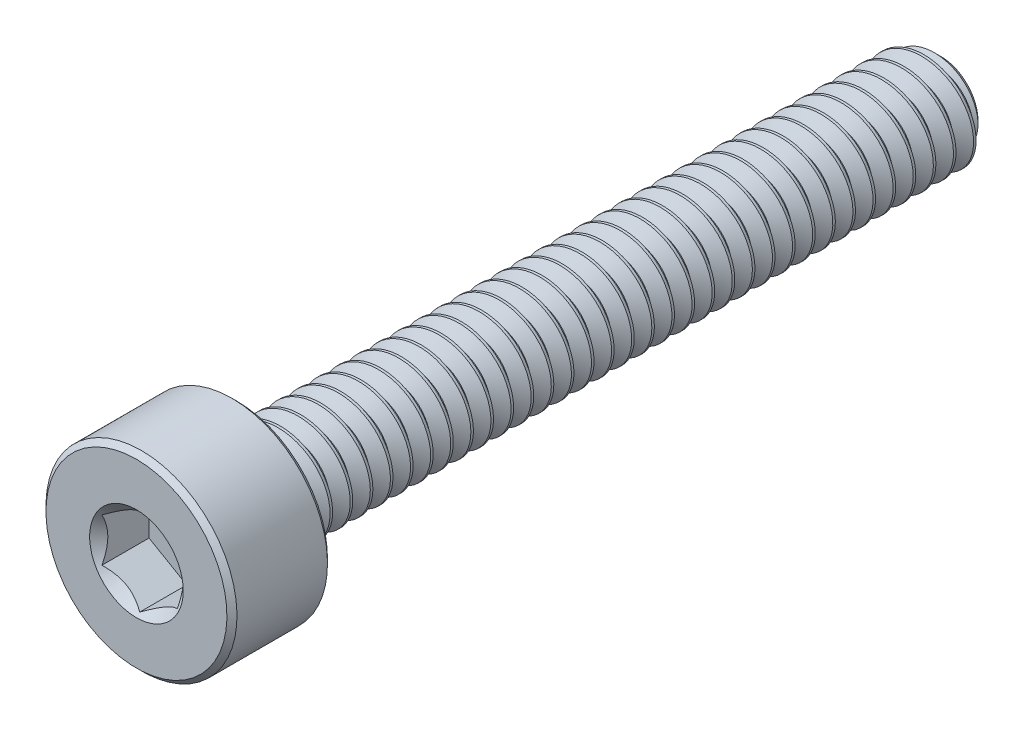
SolidWorks part; units mm, degrees
ref_plane "Front Plane" through (0, 0, 0) normal (0, 0, 1) x (1, 0, 0)
ref_plane "Top Plane" through (0, 0, 0) normal (0, 1, 0) x (1, 0, 0)
ref_plane "Right Plane" through (0, 0, 0) normal (1, 0, 0) x (0, 0, -1)
sketch "Sketch1" plane through (0, 0, 0) normal (1, 0, 0) x (0, 0, -1)
  line L0 (-8, 0) -> (8, 0) construction
  line L1 (8, 0) -> (8, 0.7402) construction
  line L2 (8, 0.7402) -> (7.7402, 1) construction
  line L3 (7.7402, 1) -> (7.7, 1) construction
  line L4 (7.7, 1) -> (-6, 1) construction
  line L5 (-6, 1) -> (-6, 1.9) construction
  line L6 (-6, 1.9) -> (-8, 1.9) construction
  line L7 (-8, 1.9) -> (-8, 0) construction
  line L8 (8, 0.7402) -> (8, 1) construction
  line L9 (7.975, 1.0433) -> (8.175, 0.6969) construction
  line L10 (8.175, 0.6969) -> (8.375, 1.0433) construction
  line L11 (8.375, 1.0433) -> (7.975, 1.0433) construction
  line L12 (8.175, 1.0433) -> (8.175, 1) construction
  line L13 (8.175, 0.6969) -> (8.175, 0.7402) construction
  line L14 (8.15, 0.7402) -> (8.2, 0.7402) construction
  line L15 (8, 1) -> (8.35, 1) construction
  line L16 (7.9875, 1.0217) -> (8.3625, 1.0217) construction
  line L17 (8, 0) -> (8, -1) construction
  line L18 (-6.1, 1.9) -> (-6, 1.8) construction
  line L19 (-7.9, 1.9) -> (-8, 1.8) construction
  line L20 (-6, 1) -> (-6, 0) construction
  line L21 (-6, 0.5) -> (-1.3333, 0.5) construction
  line L22 (-1.3333, 0.5) -> (3.3333, 0.5) construction
  line L23 (3.3333, 0.5) -> (8, 0.5) construction
  line L24 (-1.3333, 0.5) -> (-1.3333, 1) construction
  line L25 (-1.3333, 1) -> (-1.3333, 1.9) construction
  line L26 (3.3333, 0.5) -> (3.3333, 1.9) construction
  point P0 (-8, 0.75)
  point P3 (7, 1)
  point P4 (0, 0)
  point P18 (3.3333, 1)
  point P22 (8.175, 0.7402)
  point P24 (7.7, 1)
  point P25 (8.175, 1)
  point P28 (8.175, 1.0217)
  point P29 (7, -1)
  point P30 (-1.3333, 1)
  point P31 (-7, 1.9)
  point P37 (-6.35, 1.9)
  point P38 (-7.85, 1.9)
  point P45 (-1.3333, 0.5)
  point P46 (3.3333, 0.5)
  dimension "D2" = 0.05
  dimension "D7" = 0.1
  dimension "D8" = 0.1
  dimension "D9" = 0.1
  dimension "D10" = 0.05
  dimension "D11" = 0.25
  dimension "Drive Size" = 1.5
  dimension "Head Diameter" = 3.8
  dimension "Head Height" = 2
  dimension "Thread Pitch" = 0.4
  dimension "Thread Dia" = 2
  dimension "Length" = 14
  dimension "D12" = 0.3
  dimension "D4" = 1
  dimension "D3" = 45
sketch "Sketch2" plane through (0, 0, 0) normal (1, 0, 0) x (0, 0, -1)
  line L0 (-8, 0) -> (-8, 1.8)
  line L1 (-7.9, 1.9) -> (-6.1, 1.9)
  line L2 (-6, 1.8) -> (-6, 1.1)
  line L4 (7.7402, 1) -> (8, 0.7402)
  line L5 (8, 0.7402) -> (8, 0)
  line L6 (-6, 1.9) -> (-8, 1.9) construction
  line L7 (8, 0) -> (-8, 0)
  line L8 (-7.9, 1.9) -> (-8, 1.8) construction
  line L10 (-7.9, 1.9) -> (-8, 1.8)
  line L14 (-6.1, 1.9) -> (-6, 1.8) construction
  line L16 (-6.1, 1.9) -> (-6, 1.8)
  line L17 (-6, 1) -> (-6, 1.9) construction
  line L19 (-5.9, 1) -> (7.7402, 1)
  line L20 (7.7, 1) -> (-6, 1) construction
  arc A1 (-6, 1.1) -> (-5.9, 1) centre (-5.9, 1.1) ccw
  dimension "D3" = 0.1
revolve "Revolve1" add sketch "Sketch2" angle 360 about L7
sketch "Sketch3" plane through (0, 0, 8) normal (0, 0, 1) x (1, 0, 0)
  line L1 (0.75, -0.433) -> (0.75, 0.433)
  line L2 (0.75, 0.433) -> (0, 0.866)
  line L3 (0, 0.866) -> (-0.75, 0.433)
  line L4 (-0.75, 0.433) -> (-0.75, -0.433)
  line L5 (-0.75, -0.433) -> (0, -0.866)
  line L6 (0, -0.866) -> (0.75, -0.433)
  circle A0 centre (0, 0) radius 0.75 construction
  circle A1 centre (0, 0) radius 1.9 construction
  circle A2 centre (0, 0) radius 1.9 construction
  circle A3 centre (0, 0) radius 0.866 construction
  point P13 (0, 0)
  dimension "D1" = 1.7321
extrude "Cut-Extrude1" cut sketch "Sketch3" against normal offset from surface (1 mm away) 1 up to face at (0, 1.8, 6)
sketch "Sketch4" plane through (0, 0, 8) normal (0, 0, 1) x (1, 0, 0)
  circle A0 centre (0, 0) radius 0.931
  dimension "D1" = 1.862
extrude "Cut-Extrude2" cut sketch "Sketch4" against normal up to vertex (1 mm away) draft 45 up to point (0, 1.9, 7)
sketch "Sketch11" plane through (0, 0, 0) normal (1, 0, 0) x (0, 0, -1)
  line L0 (-8, 0) -> (8, 0) construction
  line L1 (-8, 0) -> (8, 0) construction
  line L2 (-3.375, 0) -> (-3.375, 1) construction
  line L3 (7.7, 1) -> (-6, 1) construction
  line L4 (5.375, 0) -> (5.375, 1) construction
  line L6 (8, 0.7402) -> (8, 1) construction
  point P2 (-3.375, 0)
  point P3 (5.375, 0)
  dimension "D1" = 2.625
  dimension "D2" = 2.625
sketch "Sketch6" plane through (0, 0, -8) normal (0, 0, -1) x (-1, 0, 0)
  circle A0 centre (0, 0) radius 1
curve "Helix/Spiral1" pitch 0.4 height 14.4 turns 36
sketch "Sketch10" plane through (0, 0, 0) normal (1, 0, 0) x (0, 0, -1)
  line L0 (-5.9, -1.9) -> (-5.9, 1.9)
  line L5 (-8, 0) -> (8, 0) construction
  line L6 (-5.9, 1) -> (-5.9, -1) construction
  point P3 (-5.9, 0)
split "Split1" trim tools "Sketch10" bodies to split 106 resulting bodies 114 115
sketch "Sketch7" plane through (0, 0, 0) normal (1, 0, 0) x (0, 0, -1)
  line L0 (7.9875, 1.0217) -> (8.3625, 1.0217)
  line L1 (8.3625, 1.0217) -> (8.2, 0.7402)
  line L2 (8.2, 0.7402) -> (8.15, 0.7402)
  line L3 (8.15, 0.7402) -> (7.9875, 1.0217)
sweep "Cut-Sweep1" cut profiles "Sketch7" path "Helix/Spiral1"
sketch "Sketch8" plane through (0, 0, 0) normal (1, 0, 0) x (0, 0, -1)
  line L0 (-6, 0) -> (-6, 1)
  line L1 (-5.9, -1) -> (-5.9, 1) construction
  line L2 (-6, 1) -> (-5.9, 1)
  line L4 (-5.9, 1) -> (-5.3226, 0)
  line L5 (-5.3226, 0) -> (-6, 0)
  line L6 (7.7, 1) -> (-6, 1) construction
  line L7 (-8, 0) -> (8, 0) construction
  dimension "D1" = 60
revolve "Revolve2" add sketch "Sketch8" angle 360 about L5
equation "\"D2@Sketch1\" = \"Thread Pitch@Sketch1\" / 8"
equation "\"D4@Helix/Spiral1\" = \"Thread Pitch@Sketch1\""
equation "\"D7@Sketch1\" = \"Head Height@Sketch1\" * .05"
equation "\"D8@Sketch1\"=\"D7@Sketch1\""
equation "\"D9@Sketch1\"=\"D7@Sketch1\""
equation "\"D10@Sketch1\"=\"D7@Sketch1\"/2"
equation "\"D11@Sketch1\"=\"D10@Sketch1\"*5"
equation "\"D4@Sketch1\"=\"Thread Pitch@Sketch1\"*2.5"
equation "\"D12@Sketch1\"=\"Thread Pitch@Sketch1\"*.75"
equation "\"D3@Helix/Spiral1\"=\"Length@Sketch1\"+\"Thread Pitch@Sketch1\""
equation "\"D3@Sketch2\"=\"Thread Dia@Sketch1\"*0.05"
equation "\"D1@Sketch11\"=\"Length@Sketch1\"*0.1875"
equation "\"D2@Sketch11\"=\"D1@Sketch11\""
equation "\"D1@Sketch4\"=\"D1@Sketch3\"*1.075"
